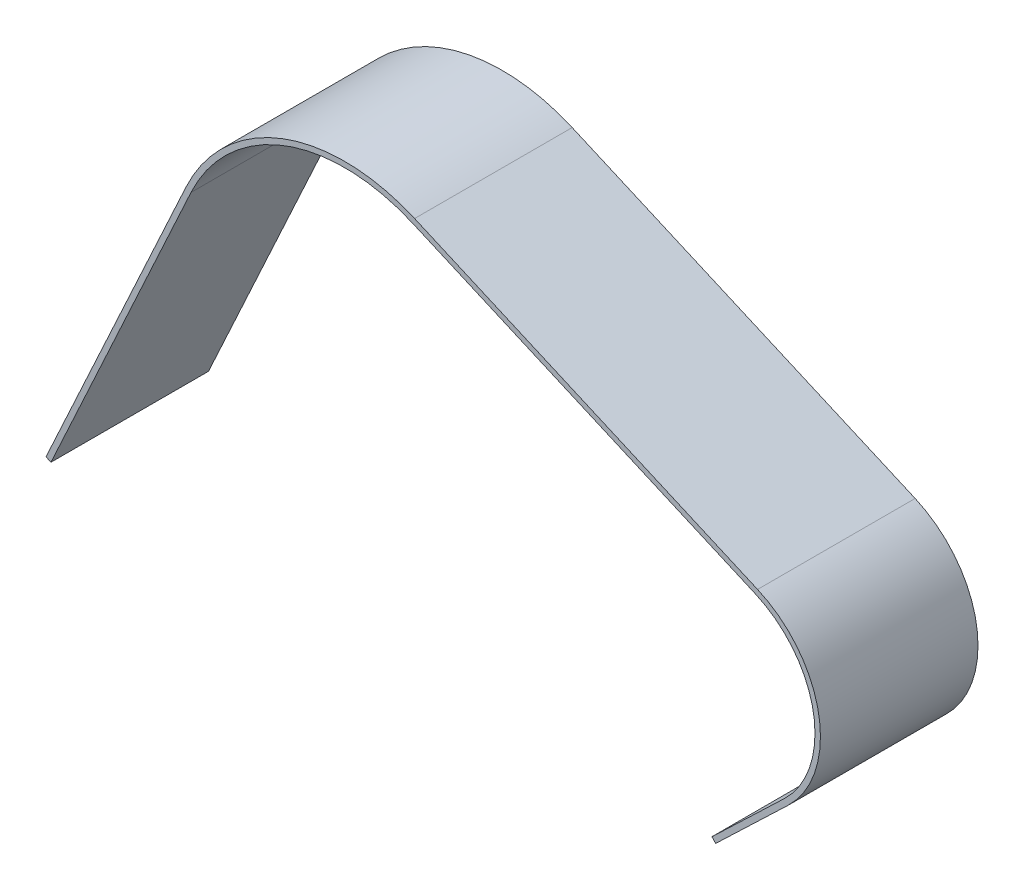
SolidWorks part; units mm, degrees
ref_plane "Front Plane" through (0, 0, 0) normal (0, 0, 1) x (1, 0, 0)
ref_plane "Top Plane" through (0, 0, 0) normal (0, 1, 0) x (1, 0, 0)
ref_plane "Right Plane" through (0, 0, 0) normal (1, 0, 0) x (0, 0, -1)
sketch "Sketch1" plane through (0, 0, 0) normal (0, 0, 1) x (1, 0, 0)
  line L0 (0, 0) -> (-431.8, 0) construction
  line L1 (-431.8, 0) -> (-341.5021, 195.812)
  line L3 (-341.5021, 195.812) -> (-320.2119, 185.994) construction
  line L6 (-431.8, 0) -> (-428.6142, -1.4691)
  line L8 (-338.3164, 194.3429) -> (-428.6142, -1.4691)
  line L9 (0, 0) -> (0.0012, -0.0035)
  line L13 (-55.6288, 0) -> (-55.6288, 82.4332) construction
  line L15 (0, 0) -> (0, 93.4448) construction
  line L16 (0.0012, -0.0035) -> (46.6772, 44.612)
  line L17 (27.024, 155.3569) -> (23.3392, 146.9151) construction
  line L18 (46.6772, 44.612) -> (27.6702, 64.4967) construction
  line L19 (44.2531, 47.148) -> (-2.4217, 2.5336)
  line L20 (0, 0) -> (-2.4217, 2.5336)
  line L21 (27.024, 155.3569) -> (-194.1268, 251.8868)
  line L22 (25.6206, 152.1417) -> (-195.5302, 248.6716)
  line L23 (-194.1268, 251.8868) -> (-195.7682, 248.1264) construction
  line L24 (-195.7682, 248.1264) -> (-195.7682, 152.0973) construction
  arc A2 (27.024, 155.3569) -> (46.6772, 44.612) centre (0, 93.4448) cw
  arc A3 (25.6206, 152.1417) -> (44.2531, 47.148) centre (0, 93.4448) cw
  arc A4 (-194.1268, 251.8868) -> (-341.5021, 195.812) centre (-239.1957, 148.6337) ccw
  arc A5 (-195.5302, 248.6716) -> (-338.3164, 194.3429) centre (-239.1957, 148.6337) ccw
  dimension "D1" = 431.8
  dimension "D4" = 241.3
extrude "Boss-Extrude1" add sketch "Sketch1" along normal blind 101.6
